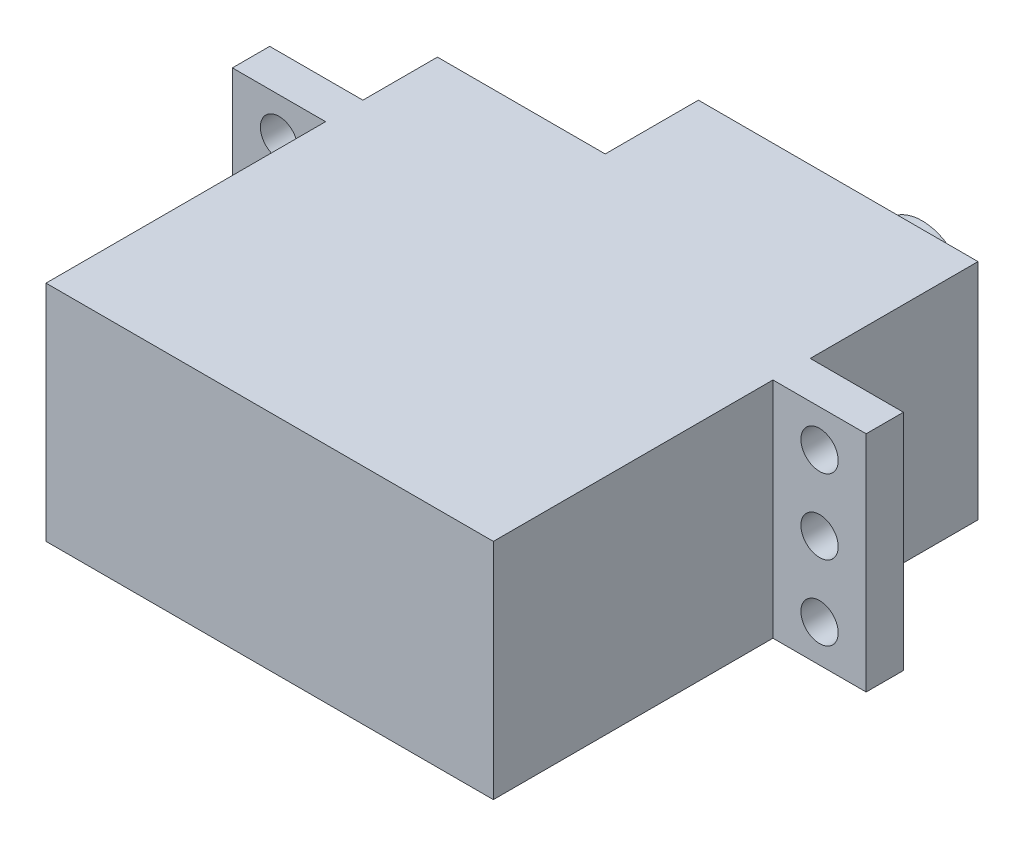
SolidWorks part; units mm, degrees
ref_plane "Front Plane" through (0, 0, 0) normal (0, 0, 1) x (1, 0, 0)
ref_plane "Top Plane" through (0, 0, 0) normal (0, 1, 0) x (1, 0, 0)
ref_plane "Right Plane" through (0, 0, 0) normal (1, 0, 0) x (0, 0, -1)
sketch "Sketch1" plane through (0, 0, 0) normal (0, 0, 1) x (1, 0, 0)
  line L1 (0, 0) -> (24, 0)
  line L2 (0, 0) -> (0, -12)
  line L3 (0, -12) -> (24, -12)
  line L4 (24, 0) -> (24, -12)
  dimension "D1" = 24
  dimension "D2" = 12
extrude "Boss-Extrude1" add sketch "Sketch1" along normal blind 21
ref_plane "Plane1" through (0, 0, 6) normal (0, 0, 1) x (1, 0, 0)
sketch "Sketch2" plane through (0, 0, 6) normal (0, 0, 1) x (1, 0, 0)
  line L0 (0, -12) -> (24, -12) construction
  line L1 (-5, 0) -> (29, 0)
  line L2 (-5, 0) -> (-5, -12)
  line L3 (-5, -12) -> (29, -12)
  line L4 (29, 0) -> (29, -12)
  line L5 (24, 0) -> (0, 0) construction
  line L6 (0, 0) -> (0, -12) construction
  line L7 (24, -12) -> (24, 0) construction
  line L8 (-3.5, -2) -> (-5, -2) construction
  line L9 (-1.5, -2) -> (0, -2) construction
  line L10 (-2.5, -1) -> (-2.5, 0) construction
  line L11 (27.5, -2) -> (29, -2) construction
  circle A0 centre (-2.5, -2) radius 1
  circle A1 centre (26.5, -2) radius 1
  circle A2 centre (26.5, -6) radius 1
  circle A3 centre (26.5, -10) radius 1
  circle A4 centre (-2.5, -6) radius 1
  circle A5 centre (-2.5, -10) radius 1
  dimension "D3" = 2
  dimension "D1" = 5
  dimension "D2" = 5
  dimension "D4" = 1
  dimension "D5" = 2
  dimension "D6" = 3
extrude "Boss-Extrude2" add sketch "Sketch2" against normal blind 2
sketch "Sketch3" plane through (0, 0, 0) normal (0, 0, -1) x (-1, 0, 0)
  line L0 (0, -12) -> (-24, -12) construction
  line L1 (-24, 0) -> (-9, 0)
  line L2 (-24, 0) -> (-24, -12)
  line L3 (-24, -12) -> (-9, -12)
  line L4 (-9, 0) -> (-9, -12)
  dimension "D1" = 15
extrude "Boss-Extrude3" add sketch "Sketch3" along normal blind 5
sketch "Sketch4" plane through (0, 0, -5) normal (0, 0, -1) x (-1, 0, 0)
  line L0 (-24, -12) -> (-24, 0) construction
  line L1 (-17, -3.6) -> (-17, 0) construction
  line L3 (-17, -8.4) -> (-17, -12) construction
  line L4 (-24, -12) -> (-9, -12) construction
  line L5 (-9, 0) -> (-24, 0) construction
  circle A0 centre (-17, -6) radius 2.4
  dimension "D1" = 4.8
  dimension "D2" = 7
extrude "Boss-Extrude4" add sketch "Sketch4" along normal blind 4
